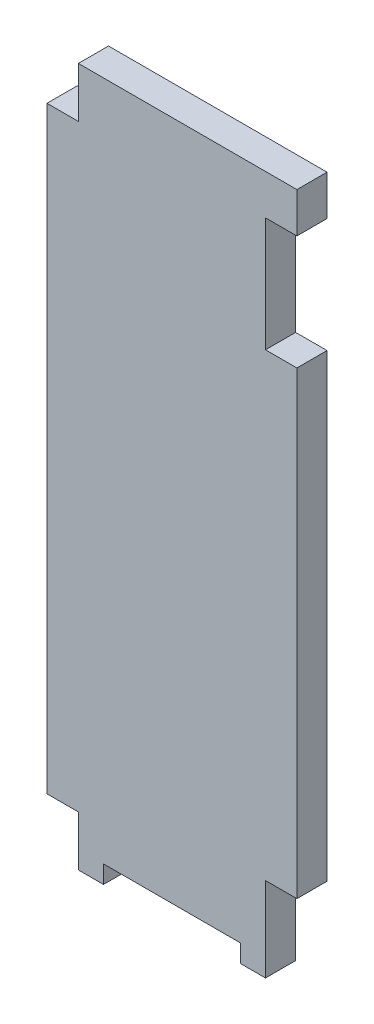
SolidWorks part; units mm, degrees
ref_plane "Front Plane" through (0, 0, 0) normal (0, 0, 1) x (1, 0, 0)
ref_plane "Top Plane" through (0, 0, 0) normal (0, 1, 0) x (1, 0, 0)
ref_plane "Right Plane" through (0, 0, 0) normal (1, 0, 0) x (0, 0, -1)
sketch "Sketch1" plane through (0, 0, 0) normal (0, 0, 1) x (1, 0, 0)
  line L0 (0, 6.731) -> (-3.175, 6.731)
  line L1 (-3.175, 6.731) -> (-3.175, -1.8034)
  line L4 (-3.175, -1.8034) -> (-5.715, -1.8034)
  line L5 (-5.715, -1.8034) -> (-5.715, 0)
  line L6 (-5.715, 0) -> (-19.558, 0)
  line L7 (-19.558, 0) -> (-19.558, -1.8034)
  line L16 (-19.558, -1.8034) -> (-22.098, -1.8034)
  line L17 (-22.098, -1.8034) -> (-22.098, 3.2766)
  line L18 (-22.098, 3.2766) -> (-25.273, 3.2766)
  line L19 (-25.273, 3.2766) -> (-25.273, 63.754)
  line L20 (-25.273, 63.754) -> (-22.098, 63.754)
  line L21 (-22.098, 63.754) -> (-22.098, 68.834)
  line L22 (-22.098, 68.834) -> (0, 68.834)
  line L23 (0, 68.834) -> (0, 64.77)
  line L24 (0, 64.77) -> (-3.175, 64.77)
  line L25 (-3.175, 64.77) -> (-3.175, 53.213)
  line L26 (-3.175, 53.213) -> (0, 53.213)
  line L27 (0, 53.213) -> (0, 6.731)
extrude "Boss-Extrude1" add sketch "Sketch1" along normal blind 3.048
